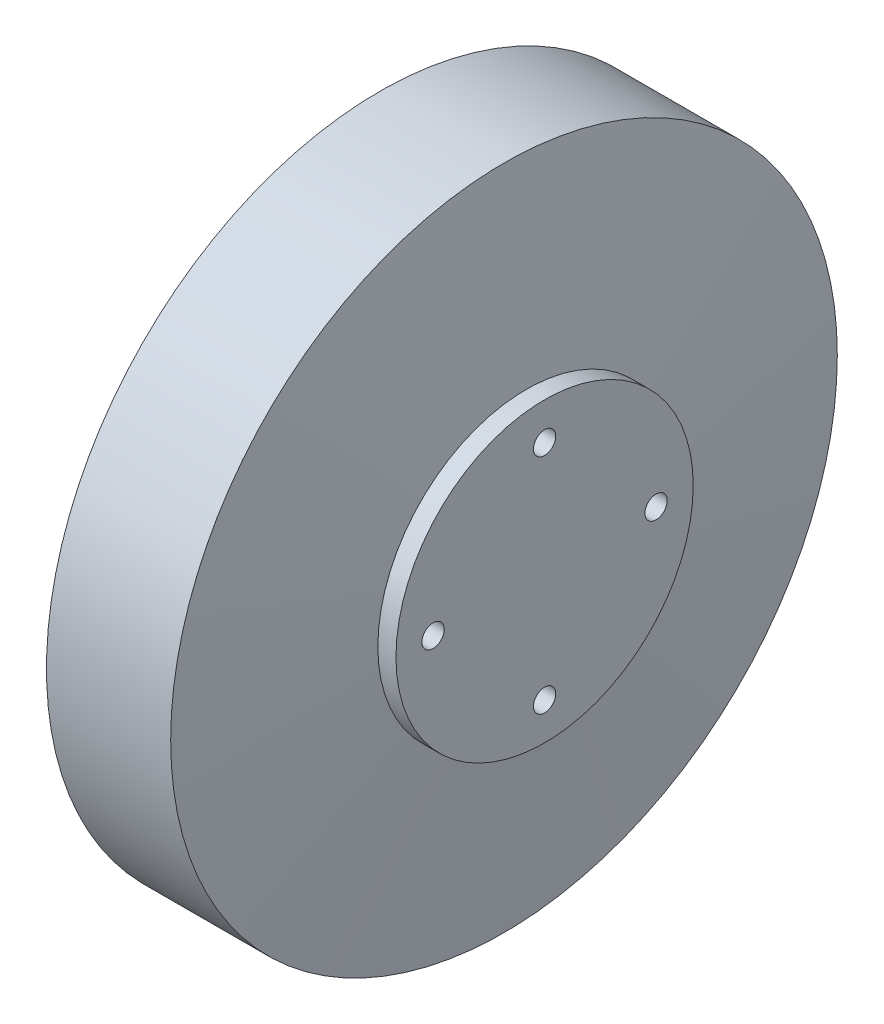
SolidWorks part; units mm, degrees
ref_plane "Front Plane" through (0, 0, 0) normal (0, 0, 1) x (1, 0, 0)
ref_plane "Top Plane" through (0, 0, 0) normal (0, 1, 0) x (1, 0, 0)
ref_plane "Right Plane" through (0, 0, 0) normal (1, 0, 0) x (0, 0, -1)
sketch "Sketch1" plane through (0, 0, 0) normal (0, 0, 1) x (1, 0, 0)
  line L1 (-5.4612, 44.85) -> (-22.1715, 44.85)
  line L2 (-22.1715, 44.85) -> (-22.1715, 42.35)
  line L3 (-22.1715, 42.35) -> (-7.1715, 42.35)
  line L6 (-11.1715, 7.5) -> (-11.1715, 0)
  line L8 (0, 0) -> (-25.7718, 0) construction
  line L10 (-11.1715, 0) -> (0, 0)
  line L12 (-11.1715, 7.5) -> (-7.1715, 7.5)
  line L13 (-7.1715, 7.5) -> (-3.1715, 9.5)
  line L14 (0, 0) -> (-5.4612, 44.85)
  line L15 (-7.1715, 42.35) -> (-3.1715, 9.5)
  point P1 (-2.171, 9.386)
  point P2 (0, 0)
  point P4 (0, 0)
  point P12 (0, 0)
  point P13 (0, 0)
  point P14 (-0.4359, 0)
  dimension "D1" = 4
  dimension "D2" = 44.85
  dimension "D3" = 15
  dimension "D4" = 2.5
  dimension "D5" = 4
  dimension "D6" = 7.5
  dimension "D9" = 2
  dimension "D10" = 2
revolve "Revolve1" add sketch "Sketch1" angle 360 about L8
sketch "Sketch2" plane through (0, 0, 0) normal (1, 0, 0) x (0, 0, -1)
  circle A0 centre (0, 15) radius 1.5
  circle A1 centre (0, -15) radius 1.5
  circle A2 centre (15, 0) radius 1.5
  circle A3 centre (-15, 0) radius 1.5
  circle A4 centre (0, 0) radius 15 construction
  circle A5 centre (0, 0) radius 20
  point P11 (16.1096, -1.4836)
  point P14 (0, 0)
  dimension "D1" = 3
  dimension "D2" = 30
  dimension "D3" = 40
extrude "Boss-Extrude3" add sketch "Sketch2<6>" against normal up to body separate body
sketch "Sketch2<6>" plane through (0, 0, 0) normal (1, 0, 0) x (0, 0, -1) same geometry as "Sketch2"
extrude "Cut-Extrude1" cut sketch "Sketch2" against normal through all and the other way through all contours A1 | A3 | A0 | A2 region at (0, 15, 0) region at (0, -15, 0) region at (0, 0, -15) region at (0, 0, 15)
ref_plane "Plane1" through (0, 0, 42.35) normal (0, 0, -1) x (-1, 0, 0)
sketch "Sketch3" plane through (0, 0, 42.35) normal (0, 0, -1) x (-1, 0, 0)
  line L0 (9, 0) -> (22.1715, 0) construction
  line L1 (22.1715, -44.85) -> (22.1715, 44.85) construction
  line L3 (20.5858, 2.5) -> (10.5858, 2.5)
  line L4 (20.5858, 2.5) -> (20.5858, -2.5)
  line L5 (20.5858, -2.5) -> (10.5858, -2.5)
  line L6 (10.5858, 2.5) -> (10.5858, -2.5)
  line L7 (20.5858, 2.5) -> (10.5858, -2.5) construction
  line L8 (20.5858, -2.5) -> (10.5858, 2.5) construction
  point P5 (5, 0)
  point P7 (15.5858, 0)
  dimension "D1" = 9
  dimension "D2" = 5
  dimension "D3" = 10
extrude "Boss-Extrude1" add sketch "Sketch3" along normal blind 1
pattern_circular "CirPattern1" count 42 over 360 about axis through (-11.1715, 0, 0) along (1, 0, 0) of "Boss-Extrude1"
hole_wizard "M2 Clearance Hole1" positions "Sketch7" profile "Sketch8" hole size "M2" standard "ANSI Metric"
sketch "Sketch7" plane through (-11.1715, 0, 0) normal (-1, 0, 0) x (0, 0, 1)
  point P0 (0, 0)
sketch "Sketch8" plane through (-11.1715, 0, 0) normal (0, 1, 0) x (0, 0, 1)
  line L0 (0, 0) -> (0, 5.721)
  line L1 (0, 5.721) -> (1.2, 5)
  line L2 (1.2, 5) -> (1.2, 0)
  line L5 (1.2, 0) -> (0, 0)
  line L10 (0, 5.721) -> (-1.2, 5) construction
  line L11 (0, -6.35) -> (0, 107.95) construction
  dimension "Hole Dia." = 2.4
  dimension "Hole Depth" = 5
  dimension "Drill Angle" = 118
